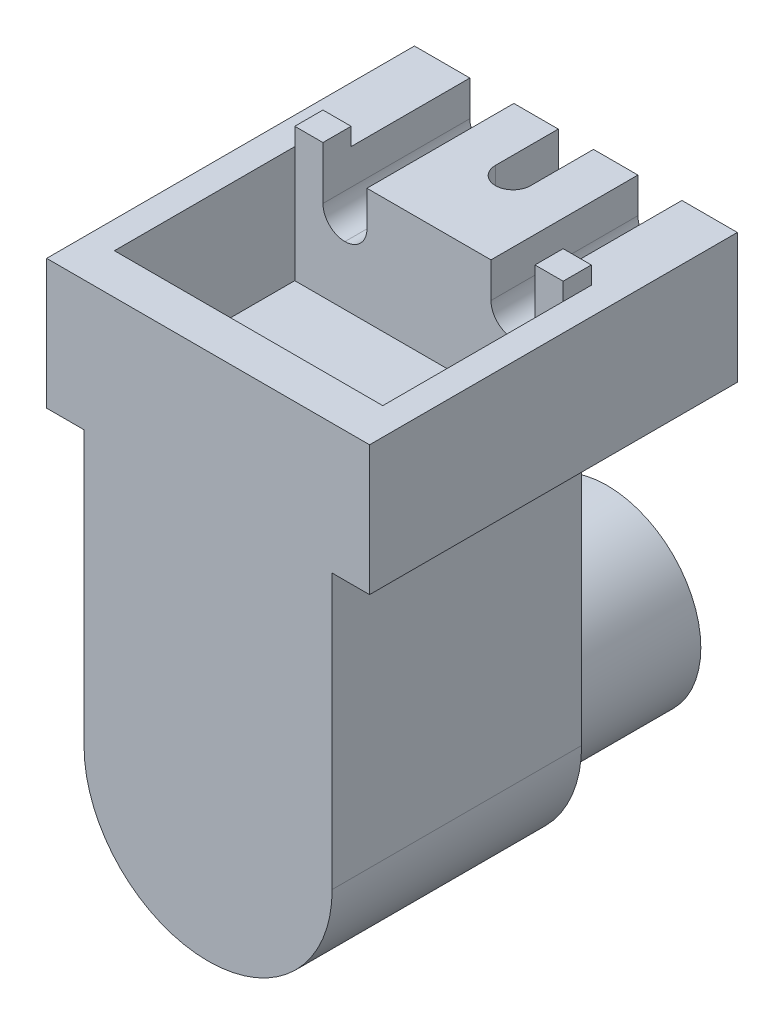
SolidWorks part; units mm, degrees
ref_plane "Plano frontal" through (0, 0, 0) normal (0, 0, 1) x (1, 0, 0)
ref_plane "Plano superior" through (0, 0, 0) normal (0, 1, 0) x (1, 0, 0)
ref_plane "Plano direito" through (0, 0, 0) normal (1, 0, 0) x (0, 0, -1)
sketch "Esboço1" plane through (0, 0, 0) normal (0, 0, 1) x (1, 0, 0)
  line L0 (0, 29.2752) -> (0, -37.2264) construction
  line L2 (14.1, -8.525) -> (14.1, 22.625)
  line L3 (14.1, 22.625) -> (-14.1, 22.625)
  line L4 (-14.1, -8.525) -> (-14.1, 22.625)
  line L5 (10.8926, -17.4783) -> (-14.1, 22.625) construction
  line L6 (14.1, 22.625) -> (-10.8926, -17.4783) construction
  arc A0 (-14.1, -8.525) -> (14.1, -8.525) centre (0, -8.525) ccw
  point P0 (0, 0)
extrude "Ressalto-extrusão1" add sketch "Esboço1" along normal blind 28.35
sketch "Esboço3" plane through (0, 22.625, 0) normal (0, 1, 0) x (1, 0, 0)
  line L5 (0, 19.6491) -> (0, -44.0768) construction
  line L6 (14.1, -28.35) -> (-14.1, -28.35) construction
  line L7 (18.35, -28.35) -> (-18.35, -28.35)
  line L8 (18.35, -28.35) -> (18.35, 13.45)
  line L9 (18.35, 13.45) -> (-18.35, 13.45)
  line L10 (-18.35, -28.35) -> (-18.35, 13.45)
  line L11 (18.35, -28.35) -> (-18.35, 13.45) construction
  line L12 (18.35, 13.45) -> (-18.35, -28.35) construction
  point P2 (0, -7.45)
  dimension "D1" = 36.7
  dimension "D2" = 41.8
extrude "Ressalto-extrusão2" add sketch "Esboço3" along normal blind 14.75
sketch "Esboço5" plane through (0, 37.375, 0) normal (0, 1, 0) x (1, 0, 0)
  line L0 (0, 23.3821) -> (0, -37.1575) construction
  line L1 (-18.35, -28.35) -> (18.35, -28.35) construction
  line L2 (15.25, -23.75) -> (-15.25, -23.75)
  line L3 (15.25, -23.75) -> (15.25, -3.25)
  line L4 (15.25, -3.25) -> (-15.25, -3.25)
  line L5 (-15.25, -23.75) -> (-15.25, -3.25)
  line L6 (15.25, -23.75) -> (-15.25, -3.25) construction
  line L7 (15.25, -3.25) -> (-15.25, -23.75) construction
  point P3 (0, -13.5)
  dimension "D1" = 20.5
  dimension "D2" = 30.5
  dimension "D3" = 4.6
extrude "Corte-extrusão2" cut sketch "Esboço5" against normal blind 13.2
sketch "Esboço6" plane through (0, 37.375, 0) normal (0, 1, 0) x (1, 0, 0)
  line L0 (0, 19.3367) -> (0, -34.7053) construction
  line L1 (-2, 13.45) -> (-2, 6.3084)
  line L2 (18.35, 13.45) -> (-18.35, 13.45) construction
  line L3 (2, 13.45) -> (2, 6.3084)
  line L4 (-2, 13.45) -> (2, 13.45)
  arc A0 (-2, 6.3084) -> (2, 6.3084) centre (0, 6.3084) ccw
  dimension "D1" = 2
extrude "Corte-extrusão3" cut sketch "Esboço6" against normal through all
sketch "Esboço7" plane through (0, 37.375, 0) normal (0, 1, 0) x (1, 0, 0)
  line L0 (0, 21.5234) -> (0, -41.1091) construction
  line L1 (-12.05, 13.45) -> (-12.05, -3.25)
  line L2 (-2, 13.45) -> (-18.35, 13.45) construction
  line L3 (15.25, -3.25) -> (-15.25, -3.25) construction
  line L4 (-12.05, -3.25) -> (-7.05, -3.25)
  line L5 (-7.05, -3.25) -> (-7.05, 13.45)
  line L6 (-7.05, 13.45) -> (-12.05, 13.45)
  line L7 (-18.35, 13.45) -> (-18.35, -28.35) construction
  line L8 (7.05, -3.25) -> (7.05, 13.45)
  line L9 (12.05, -3.25) -> (7.05, -3.25)
  line L10 (12.05, 13.45) -> (12.05, -3.25)
  line L11 (7.05, 13.45) -> (12.05, 13.45)
  dimension "D1" = 6.3
  dimension "D2" = 5
extrude "Corte-extrusão4" cut sketch "Esboço7" against normal blind 6.5
fillet "Filete1" radius 2.5 4 edges at (-12.05, 30.875, -5.1) (-7.05, 30.875, -5.1) (7.05, 30.875, -5.1) (12.05, 30.875, -5.1)
sketch "Esboço8" plane through (0, 0, -13.45) normal (0, 0, -1) x (-1, 0, 0)
  line L0 (0, 41.7799) -> (0, 10.4982) construction
  line L1 (-21.2908, 30) -> (21.3757, 30) construction
  line L3 (4.2925, 28.25) -> (-4.2075, 28.25)
  line L4 (4.2925, 28.25) -> (4.2925, 31.75)
  line L5 (4.2925, 31.75) -> (-4.2075, 31.75)
  line L6 (-4.2075, 28.25) -> (-4.2075, 31.75)
  line L7 (4.2925, 28.25) -> (-4.2075, 31.75) construction
  line L8 (4.2925, 31.75) -> (-4.2075, 28.25) construction
  point P5 (0.0425, 30)
  dimension "D1" = 3.5
  dimension "D2" = 8.5
extrude "Corte-extrusão5" cut sketch "Esboço8" against normal blind 14
sketch "Esboço9" plane through (0, 37.375, 0) normal (0, 1, 0) x (1, 0, 0)
  line L0 (-12.05, 13.45) -> (-12.05, -3.25) construction
  line L1 (-15.25, -3.25) -> (-12.05, -3.25)
  line L2 (-15.25, -3.25) -> (-15.25, -0.05)
  line L3 (-15.25, -0.05) -> (-12.05, -0.05)
  line L4 (-12.05, -3.25) -> (-12.05, -0.05)
  line L5 (0, 16.9982) -> (0, -34.4251) construction
  line L6 (15.25, -0.05) -> (12.05, -0.05)
  line L7 (12.05, -3.25) -> (12.05, -0.05)
  line L8 (15.25, -3.25) -> (12.05, -3.25)
  line L9 (15.25, -3.25) -> (15.25, -0.05)
extrude "Ressalto-extrusão3" add sketch "Esboço9" along normal blind 2
sketch "Esboço10" plane through (0, 0, 0) normal (0, 0, -1) x (-1, 0, 0)
  line L0 (0, -28.7084) -> (0, 47.2281) construction
  circle A0 centre (0, -9.125) radius 10.65
  arc A1 (-14.1, -8.525) -> (14.1, -8.525) centre (0, -8.525) ccw construction
  point P5 (0, -22.625)
  dimension "D1" = 21.3
  dimension "D2" = 13.5
extrude "Ressalto-extrusão4" add sketch "Esboço10" along normal blind 17
sketch "Esboço11" plane through (0, 0, -17) normal (0, 0, -1) x (-1, 0, 0)
  line L0 (0, 4.5613) -> (0, -25.0555) construction
  line L1 (-12.1779, -9.125) -> (12.4924, -9.125) construction
  circle A0 centre (0, -9.125) radius 4.25
  dimension "D1" = 8.5
extrude "Corte-extrusão6" cut sketch "Esboço11" against normal blind 25
